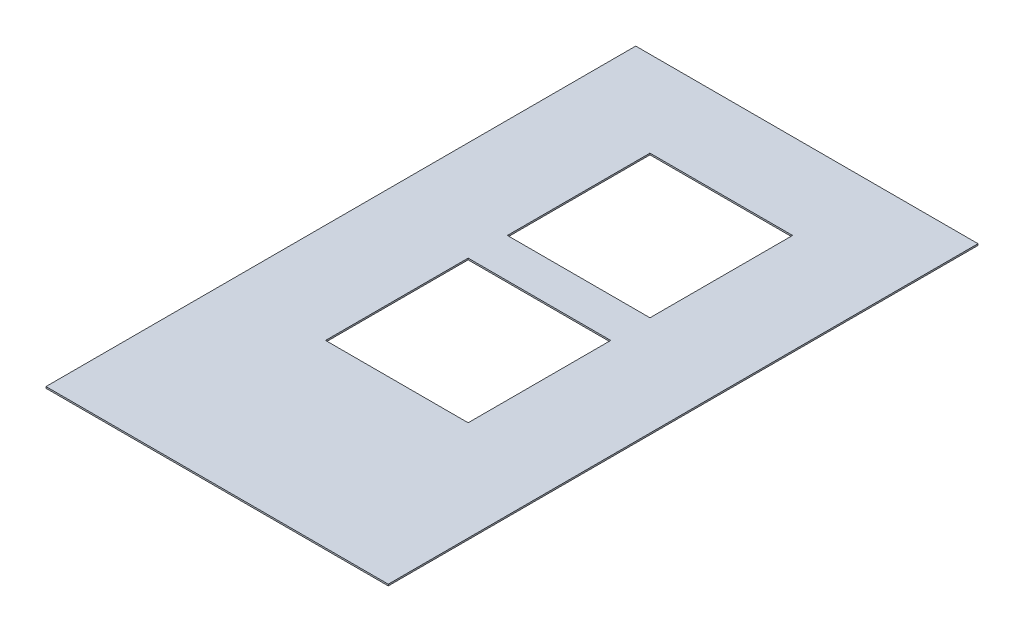
SolidWorks part; units mm, degrees
material "Teak"
ref_plane "Front Plane" through (0, 0, 0) normal (0, 0, 1) x (1, 0, 0)
ref_plane "Top Plane" through (0, 0, 0) normal (0, 1, 0) x (1, 0, 0)
ref_plane "Right Plane" through (0, 0, 0) normal (1, 0, 0) x (0, 0, -1)
sketch "Sketch1" plane through (0, 0, 0) normal (0, 1, 0) x (1, 0, 0)
  line L1 (-609.6, -1050.29) -> (609.6, -1050.29)
  line L2 (-609.6, -1050.29) -> (-609.6, 1050.29)
  line L3 (-609.6, 1050.29) -> (609.6, 1050.29)
  line L4 (609.6, -1050.29) -> (609.6, 1050.29)
  line L5 (-609.6, -1050.29) -> (609.6, 1050.29) construction
  line L6 (-609.6, 1050.29) -> (609.6, -1050.29) construction
  point P0 (0, 0)
  dimension "D1" = 1219.2
  dimension "D2" = 2100.58
extrude "Boss-Extrude1" add sketch "Sketch1" along normal blind 5.5562
sketch "Sketch2" plane through (0, 0, 0) normal (0, -1, 0) x (-1, 0, 0)
  line L1 (-254, 237.49) -> (254, 237.49)
  line L2 (-254, 237.49) -> (-254, 745.49)
  line L3 (-254, 745.49) -> (254, 745.49)
  line L4 (254, 237.49) -> (254, 745.49)
  line L5 (-254, 237.49) -> (254, 745.49) construction
  line L6 (-254, 745.49) -> (254, 237.49) construction
  line L7 (-254, -410.21) -> (254, -410.21)
  line L8 (-254, -410.21) -> (-254, 97.79)
  line L9 (-254, 97.79) -> (254, 97.79)
  line L10 (254, -410.21) -> (254, 97.79)
  line L11 (-254, -410.21) -> (254, 97.79) construction
  line L12 (-254, 97.79) -> (254, -410.21) construction
  point P0 (0, 491.49)
  point P6 (0, -156.21)
  dimension "D1" = 508
extrude "Cut-Extrude1" cut sketch "Sketch2" against normal through all both and the other way through all
